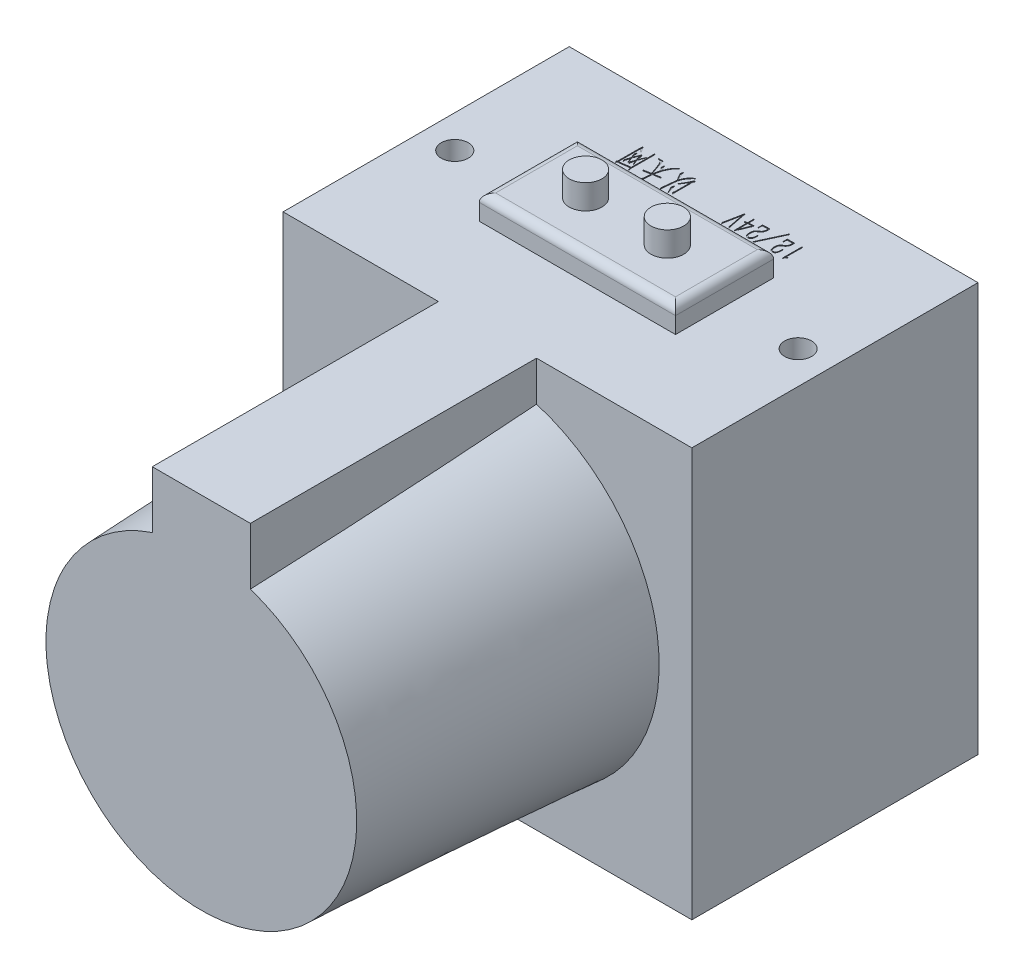
SolidWorks part; units mm, degrees
ref_plane "前视基准面" through (0, 0, 0) normal (0, 0, 1) x (1, 0, 0)
ref_plane "上视基准面" through (0, 0, 0) normal (0, 1, 0) x (1, 0, 0)
ref_plane "右视基准面" through (0, 0, 0) normal (1, 0, 0) x (0, 0, -1)
sketch "草图1" plane through (0, 0, 0) normal (0, 0, 1) x (1, 0, 0)
  line L1 (-25, -25) -> (25, -25)
  line L2 (-25, -25) -> (-25, 25)
  line L3 (-25, 25) -> (25, 25)
  line L4 (25, -25) -> (25, 25)
  line L5 (-25, -25) -> (25, 25) construction
  line L6 (-25, 25) -> (25, -25) construction
  point P0 (0, 0)
  dimension "D1" = 50
  dimension "D2" = 50
extrude "凸台-拉伸1" add sketch "草图1" along normal blind 35
ref_plane "基准面1" through (0, 0, 70) normal (0, 0, -1) x (-1, 0, 0)
sketch "草图3" plane through (0, 0, 70) normal (0, 0, -1) x (-1, 0, 0)
  circle A0 centre (0, 0) radius 19
  dimension "D1" = 38
sketch "草图4" plane through (0, 0, 35) normal (0, 0, 1) x (1, 0, 0)
  circle A0 centre (0, 0) radius 21
  dimension "D1" = 42
loft "放样1" add profiles "草图3", "草图4" connector at (18.5605, -4.0631, 70) connector at (20.9916, 0.5937, 35)
sketch "草图5" plane through (0, 0, 35) normal (0, 0, 1) x (1, 0, 0)
  line L0 (25, 25) -> (-25, 25) construction
  line L1 (-6, 25) -> (6, 25)
  line L2 (-6, 25) -> (-6, 16)
  line L3 (-6, 16) -> (6, 16)
  line L4 (6, 25) -> (6, 16)
  line L5 (0, 0) -> (0, 30.0821) construction
  dimension "D1" = 12
  dimension "D2" = 9
extrude "凸台-拉伸2" add sketch "草图5" along normal up to surface (35 mm away) up to face at (-19, 0, 70)
hole_wizard "M4 螺纹孔的螺纹孔钻头1" positions "草图6" profile "草图7" hole size "M4" standard "GB"
sketch "草图6" plane through (0, 25, 0) normal (0, 1, 0) x (1, 0, 0)
  line L0 (21, -18) -> (-21, -18) construction
  line L2 (25, 0) -> (-25, 0) construction
  line L4 (0, 0) -> (0, -18) construction
  point P0 (21, -18)
  point P2 (-21, -18)
  dimension "D1" = 18
  dimension "D2" = 42
sketch "草图7" plane through (21, 25, 18) normal (1, 0, 0) x (0, 0, 1)
  line L0 (0, 0) -> (0, 6.9914)
  line L1 (0, 6.9914) -> (1.65, 6)
  line L2 (1.65, 6) -> (1.65, 0)
  line L5 (1.65, 0) -> (0, 0)
  line L10 (0, 6.9914) -> (-1.65, 6) construction
  line L11 (0, -6.35) -> (0, 107.95) construction
  dimension "孔直径" = 3.3
  dimension "孔深度" = 6
  dimension "导头角度" = 118
sketch "草图8" plane through (0, 25, 0) normal (0, 1, 0) x (1, 0, 0)
  line L0 (21, -18) -> (-21, -18) construction
  line L1 (12, -24) -> (-12, -24)
  line L2 (12, -24) -> (12, -12)
  line L3 (12, -12) -> (-12, -12)
  line L4 (-12, -24) -> (-12, -12)
  line L5 (12, -24) -> (-12, -12) construction
  line L6 (12, -12) -> (-12, -24) construction
  point P0 (0, -18)
  dimension "D1" = 12
  dimension "D2" = 24
extrude "凸台-拉伸3" add sketch "草图8" along normal blind 3
fillet "圆角1" radius 1 4 edges at (0, 28, 12) (12, 28, 18) (0, 28, 24) (-12, 28, 18)
sketch "草图9" plane through (0, 28, 0) normal (0, 1, 0) x (1, 0, 0)
  line L0 (-11, -18) -> (11, -18) construction
  line L1 (-11, -13) -> (-11, -23) construction
  line L2 (11, -23) -> (11, -13) construction
  line L3 (0, -13) -> (0, -18) construction
  line L4 (11, -13) -> (-11, -13) construction
  circle A0 centre (-5, -18) radius 2
  circle A1 centre (5, -18) radius 2
  dimension "D1" = 4
  dimension "D2" = 10
extrude "凸台-拉伸4" add sketch "草图9" along normal blind 3
hole_wizard "M3 螺纹孔1" positions "草图10" profile "草图11" tap size "M3" standard "GB"
sketch "草图10" plane through (0, 0, 0) normal (0, 0, -1) x (-1, 0, 0)
  line L0 (0, 0) -> (8.1286, 0) construction
  line L2 (0, 0) -> (0, 9.295) construction
  point P0 (20, 20)
  point P2 (-20, -20)
  dimension "D1" = 40
  dimension "D2" = 40
  dimension "D3" = 20
  dimension "D4" = 20
sketch "草图11" plane through (-20, 20, 0) normal (1, 0, 0) x (0, 1, 0)
  line L0 (0, 0) -> (0, 9.2511)
  line L1 (0, 9.2511) -> (1.25, 8.5)
  line L2 (1.25, 8.5) -> (1.25, 0)
  line L5 (1.25, 0) -> (0, 0)
  line L10 (0, 9.2511) -> (-1.25, 8.5) construction
  line L11 (0, -6.35) -> (0, 107.95) construction
  dimension "螺纹孔钻头直径" = 2.5
  dimension "螺纹孔钻头深度" = 8.5
  dimension "导头角度" = 118
cosmetic thread "孔螺蚊线1" parameters "D1"=6, "D2"=3
cosmetic thread "孔螺蚊线2" parameters "D1"=6, "D2"=3
sketch "草图12" plane through (0, 28, 0) normal (0, 1, 0) x (1, 0, 0)
  line L0 (11.131, -6.7904) -> (-11.1614, -6.7904) construction
sketch "草图13" plane through (0, 25, 0) normal (0, 1, 0) x (1, 0, 0)
  text T0 "12/24V    以太网" font "汉仪长仿宋体" height in points 10
extrude "切除-拉伸1" cut sketch "草图13" against normal blind 0.1
